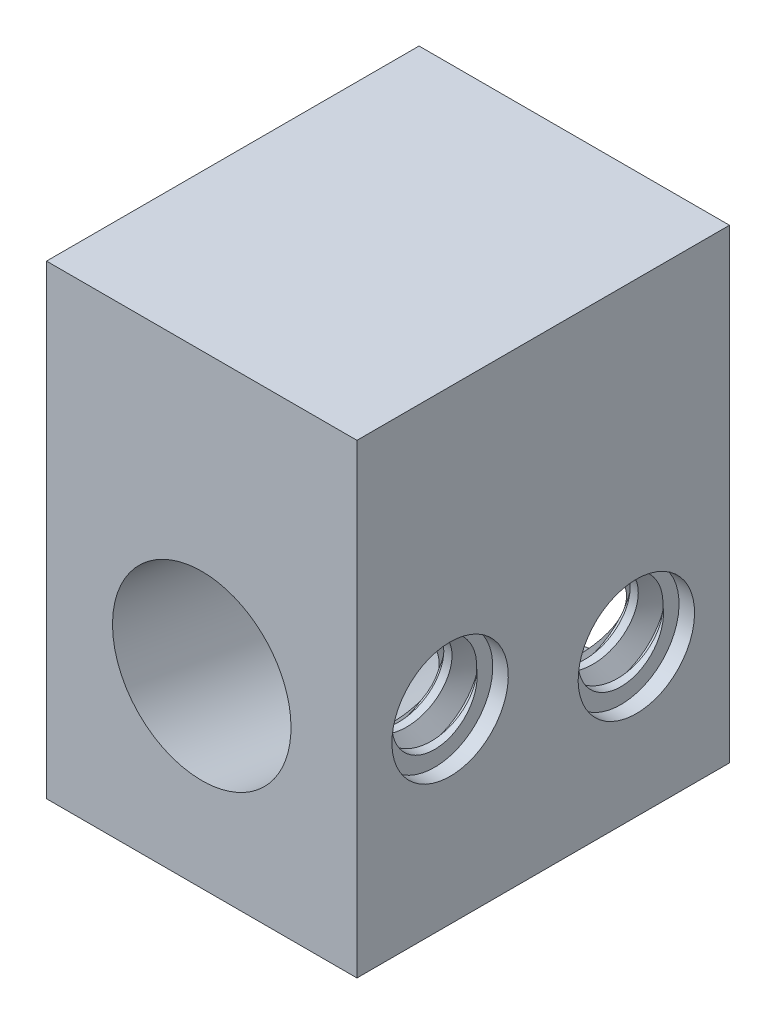
SolidWorks part; units mm, degrees
ref_plane "Front Plane" through (0, 0, 0) normal (0, 0, 1) x (1, 0, 0)
ref_plane "Top Plane" through (0, 0, 0) normal (0, 1, 0) x (1, 0, 0)
ref_plane "Right Plane" through (0, 0, 0) normal (1, 0, 0) x (0, 0, -1)
sketch "Sketch1" plane through (0, 0, 0) normal (0, 0, 1) x (1, 0, 0)
  line L1 (0, 0) -> (-20, 0)
  line L2 (0, 0) -> (0, -30)
  line L3 (0, -30) -> (-20, -30)
  line L4 (-20, 0) -> (-20, -30)
  dimension "D1" = 20
  dimension "D2" = 30
extrude "Boss-Extrude1" add sketch "Sketch1" along normal blind 24
sketch "Sketch25" plane through (0, 0, 0) normal (1, 0, 0) x (0, 0, -1)
  line L1 (0, -30) -> (0, 0) construction
  line L2 (2.2654, -16.1524) -> (0, -29)
  line L3 (0, -29) -> (0, -17)
  line L4 (2.2654, -16.1524) -> (0, -14)
  line L5 (0, -14) -> (0, -17)
  dimension "D1" = 10
  dimension "D2" = 12
  dimension "D3" = 1
  dimension "D4" = 3.1249
  dimension "D5" = 3
extrude "Boss-Extrude2" add sketch "Sketch25" against normal up to vertex (20 mm away) up to point (-20, 0, 0)
sketch "Sketch26" plane through (0, -0.8745, -4.9593) normal (0, -0.1736, -0.9848) x (-1, 0, 0)
  line L0 (20, -28.5594) -> (20, -15.5136) construction
  line L1 (20, -28.5594) -> (0, -28.5594) construction
  circle A0 centre (10, -22.0365) radius 5.75
  point P4 (20, -22.0365)
  point P7 (10, -28.5594)
  dimension "D1" = 0
  dimension "D3" = 11.5
  dimension "D2" = 0
extrude "Cut-Extrude14" cut sketch "Sketch26" against normal blind 41
sketch "Sketch8" plane through (0, 0, 0) normal (0, 0, -1) x (-1, 0, 0)
  line L0 (0, 0) -> (20, 0) construction
  circle A0 centre (10, -9.5) radius 2
  point P4 (10, 0)
  dimension "D1" = 0
  dimension "D2" = 4
  dimension "D3" = 9.5
extrude "Cut-Extrude5" cut sketch "Sketch8" against normal blind 20
sketch "Sketch13" plane through (0, 0, 0) normal (1, 0, 0) x (0, 0, -1)
  line L0 (-24, -30) -> (0, -30) construction
  line L1 (0, -30) -> (0, -29) construction
  circle A0 centre (-6, -20.5) radius 2.75
  dimension "D1" = 9.5
  dimension "D2" = 5.5
  dimension "D3" = 6
extrude "Cut-Extrude8" cut sketch "Sketch13" against normal blind 10
thread "Thread3" pitch 2.1167 method cut profile "Thread Profile3" start angle 0, offset 0, length 10, pitch 2.1167, diameter 5.5
ref_plane "Plane3" through (0, -20.5, 8.75) normal (0, -1, 0) x (0, 0, 1)
sketch "Thread Profile3" plane through (0, -20.5, 8.75) normal (0, -1, 0) x (0, 0, 1)
  line L0 (0, 0) -> (0, 2.1167) construction
  line L1 (0, 0) -> (1.1457, 0.6615)
  line L2 (1.1457, 0.6615) -> (1.1457, 0.926)
  line L3 (1.1457, 0.926) -> (0, 1.5875)
  line L4 (1.1457, 0.7937) -> (0, 0.7937) construction
  line L11 (0, 0) -> (0, 1.5875)
  point P2 (0, 0)
  dimension "Pitch" = 2.1167
  dimension "Profile_Angle" = 60
  dimension "Profile_Land" = 0.2646
  dimension "Profile_Height" = 1.1457
sketch "Sketch16" plane through (0, 0, 0) normal (1, 0, 0) x (0, 0, -1)
  circle A0 centre (-6, -20.5) radius 3.75
  dimension "D1" = 7.5
extrude "Cut-Extrude9" cut sketch "Sketch16" against normal blind 1
sketch "Sketch19" plane through (0, 0, 0) normal (1, 0, 0) x (0, 0, -1)
  line L0 (-24, -30) -> (-24, 0) construction
  line L1 (-24, -30) -> (0, -30) construction
  circle A0 centre (-18, -18) radius 2.75
  dimension "D1" = 6
  dimension "D2" = 5.5
  dimension "D3" = 12
extrude "Cut-Extrude11" cut sketch "Sketch19" against normal blind 10
thread "Thread4" pitch 2.1167 method cut profile "Thread Profile4" start angle 0, offset 0, length 10, pitch 2.1167, diameter 5.5
ref_plane "Plane4" through (0, -18, 20.75) normal (0, -1, 0) x (0, 0, 1)
sketch "Thread Profile4" plane through (0, -18, 20.75) normal (0, -1, 0) x (0, 0, 1)
  line L0 (0, 0) -> (0, 2.1167) construction
  line L1 (0, 0) -> (1.1457, 0.6615)
  line L2 (1.1457, 0.6615) -> (1.1457, 0.926)
  line L3 (1.1457, 0.926) -> (0, 1.5875)
  line L4 (1.1457, 0.7937) -> (0, 0.7937) construction
  line L11 (0, 0) -> (0, 1.5875)
  point P2 (0, 0)
  dimension "Pitch" = 2.1167
  dimension "Profile_Angle" = 60
  dimension "Profile_Land" = 0.2646
  dimension "Profile_Height" = 1.1457
sketch "Sketch22" plane through (0, 0, 0) normal (1, 0, 0) x (0, 0, -1)
  circle A0 centre (-18, -18) radius 3.75
  dimension "D1" = 7.5
extrude "Cut-Extrude12" cut sketch "Sketch22" against normal blind 1
sketch "Sketch23" plane through (0, 0, 0) normal (0, 0, -1) x (-1, 0, 0)
  line L0 (0, -30) -> (0, -29) construction
  line L1 (5, -4) -> (2, -4)
  line L2 (5, -4) -> (5, -10)
  line L3 (5, -10) -> (2, -10)
  line L4 (2, -4) -> (2, -10)
  line L5 (0, 0) -> (20, 0) construction
  dimension "D1" = 2
  dimension "D2" = 3
  dimension "D3" = 6
  dimension "D4" = 4
extrude "Cut-Extrude13" cut sketch "Sketch23" against normal blind 14
sketch "Sketch27" plane through (0, 0, 0) normal (1, 0, 0) x (0, 0, -1)
  line L1 (0, -14) -> (5.6882, -14)
  line L2 (0, -14) -> (0, -29)
  line L3 (0, -29) -> (5.6882, -29)
  line L4 (5.6882, -14) -> (5.6882, -29)
  dimension "D1" = 0
extrude "Cut-Extrude15" cut sketch "Sketch27" against normal up to vertex (20 mm away) up to point (-20, -29, 0)
